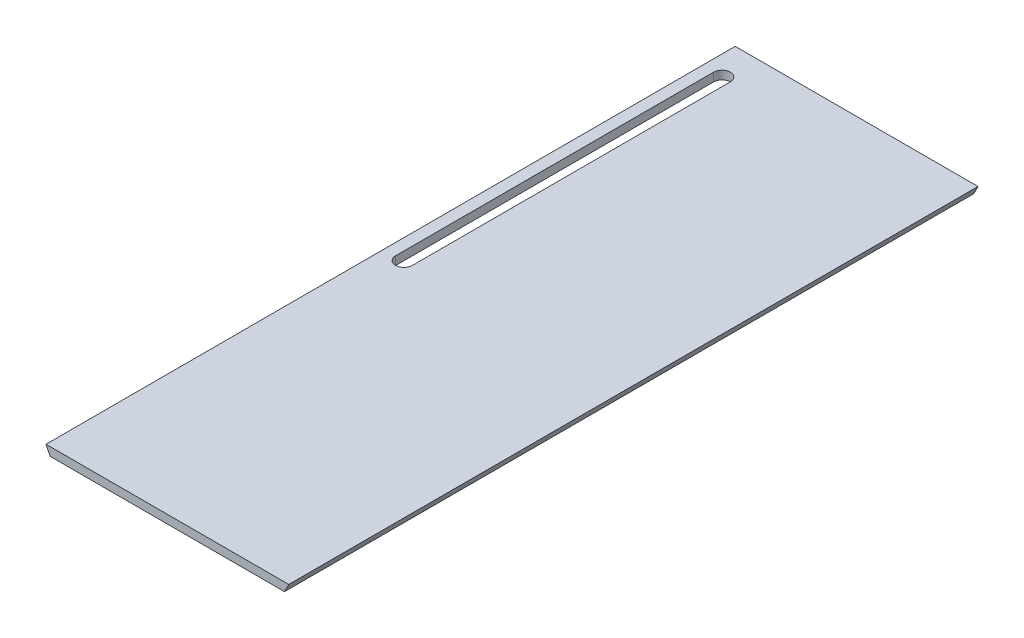
SolidWorks part; units mm, degrees
ref_plane "Front Plane" through (0, 0, 0) normal (0, 0, 1) x (1, 0, 0)
ref_plane "Top Plane" through (0, 0, 0) normal (0, 1, 0) x (1, 0, 0)
ref_plane "Right Plane" through (0, 0, 0) normal (1, 0, 0) x (0, 0, -1)
sketch "Sketch2" plane through (0, 0, 0) normal (0, 0, 1) x (1, 0, 0)
  line L1 (0, -21.393) -> (0, -24.5934) construction
  line L2 (-44.45, -24.5934) -> (44.45, -24.5934)
  line L4 (-46.0758, -21.393) -> (46.0758, -21.393)
  arc A1 (-46.0758, -21.393) -> (-44.45, -24.5934) centre (0, 0) ccw
  arc A3 (44.45, -24.5934) -> (46.0758, -21.393) centre (0, 0) ccw
  dimension "D2" = 3.2004
extrude "Boss-Extrude1" add sketch "Sketch2" along normal blind 261.62 contours L4 A3 L2 A1
sketch "Sketch3" plane through (0, -21.393, 0) normal (0, 1, 0) x (-1, 0, 0)
  line L1 (38.5043, 9.421) -> (38.5043, 0) construction
  line L2 (46.0758, 0) -> (-46.0758, 0) construction
  line L3 (46.0758, 261.62) -> (46.0758, 0) construction
  line L4 (-46.0758, 261.62) -> (-46.0758, 0) construction
  line L5 (46.0758, 72.9493) -> (41.6793, 72.9493) construction
  line L6 (35.3293, 12.596) -> (41.6793, 12.596) construction
  line L7 (35.3293, 12.596) -> (35.3293, 133.3026)
  line L8 (35.3293, 133.3026) -> (41.6793, 133.3026) construction
  line L9 (41.6793, 12.596) -> (41.6793, 133.3026)
  arc A1 (35.3293, 133.3026) -> (41.6793, 133.3026) centre (38.5043, 133.3026) cw
  arc A2 (41.6793, 12.596) -> (35.3293, 12.596) centre (38.5043, 12.596) cw
  dimension "D1" = 9.421
  dimension "D2" = 4.3965
  dimension "D3" = 120.7066
  dimension "D4" = 6.35
extrude "Cut-Extrude1" cut sketch "Sketch3" against normal through all
